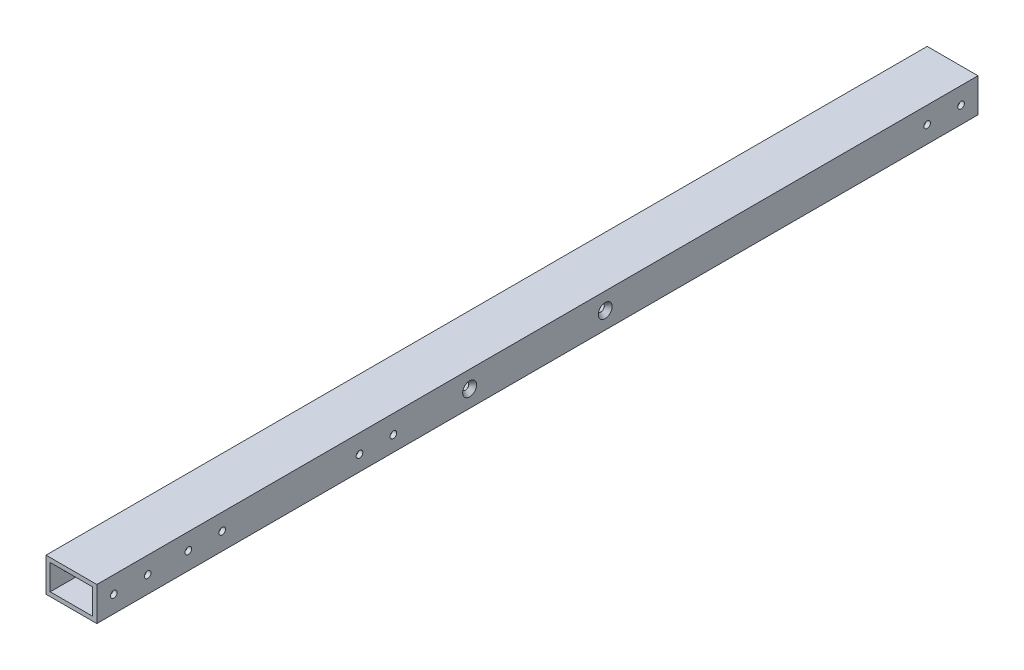
SolidWorks part; units mm, degrees
ref_plane "Front Plane" through (0, 0, 0) normal (0, 0, 1) x (1, 0, 0)
ref_plane "Top Plane" through (0, 0, 0) normal (0, 1, 0) x (1, 0, 0)
ref_plane "Right Plane" through (0, 0, 0) normal (1, 0, 0) x (0, 0, -1)
sketch "Sketch1" plane through (0, 0, 0) normal (0, 0, 1) x (1, 0, 0)
  line L0 (-15.875, 9.525) -> (15.875, 9.525)
  line L2 (-19.05, 12.7) -> (19.05, 12.7)
  line L3 (-19.05, 12.7) -> (-19.05, -12.7)
  line L4 (-19.05, -12.7) -> (19.05, -12.7)
  line L5 (19.05, 12.7) -> (19.05, -12.7)
  line L10 (15.875, 9.525) -> (15.875, -9.525)
  line L11 (-15.875, -9.525) -> (15.875, -9.525)
  line L12 (-15.875, 9.525) -> (-15.875, -9.525)
  point P12 (0, 12.7)
  point P14 (19.05, 0)
  dimension "Wall Thickness" = 3.175
  dimension "Outside Width" = 38.1
  dimension "Outside Height" = 25.4
  dimension "Inside Height" = 19.05
  dimension "Inside Width" = 31.75
sketch "Sketch2" plane through (0, 0, 0) normal (1, 0, 0) x (0, 0, -1)
  line L0 (330.2, 0) -> (-330.2, 0)
  point P4 (0, 0)
  point P7 (-330.2, 0)
  point P10 (330.2, 0)
  dimension "Length" = 660.4
sketch "Sketch3" plane through (0, 0, 0) normal (0, 0, 1) x (1, 0, 0)
  line L21 (19.05, 12.7) -> (-19.05, 12.7)
  line L22 (19.05, -12.7) -> (19.05, 12.7)
  line L23 (-19.05, -12.7) -> (19.05, -12.7)
  line L24 (-19.05, 12.7) -> (-19.05, -12.7)
  line L25 (19.05, 12.7) -> (-19.05, 12.7)
  line L26 (19.05, -12.7) -> (19.05, 12.7)
  line L27 (-19.05, -12.7) -> (19.05, -12.7)
  line L28 (-19.05, 12.7) -> (-19.05, -12.7)
  line L29 (15.875, 9.525) -> (-15.875, 9.525)
  line L30 (15.875, -9.525) -> (15.875, 9.525)
  line L31 (-15.875, -9.525) -> (15.875, -9.525)
  line L32 (-15.875, 9.525) -> (-15.875, -9.525)
  line L33 (15.875, 9.525) -> (-15.875, 9.525)
  line L34 (15.875, -9.525) -> (15.875, 9.525)
  line L35 (-15.875, -9.525) -> (15.875, -9.525)
  line L36 (-15.875, 9.525) -> (-15.875, -9.525)
  dimension "D1" = 0
  dimension "D2" = 0
extrude "Boss-Extrude1" add sketch "Sketch3" along normal up to vertex (330.2 mm away) and the other way up to vertex (330.2 mm away) up to point (0, 0, 330.2) other way up to point (0, 0, -330.2)
sketch "Drawing Reference" plane through (0, 0, 0) normal (1, 0, 0) x (0, 0, -1)
  line L0 (-330.2, 0) -> (330.2, 0) construction
  line L1 (0, -12.7) -> (0, 12.7) construction
  line L2 (-330.2, -12.7) -> (330.2, -12.7) construction
  line L5 (-330.2, 12.7) -> (330.2, 12.7) construction
  point P7 (-302.768, 0)
  point P8 (302.768, 0)
  dimension "D1" = 27.432
sketch "Sketch4" plane through (-19.05, 0, 0) normal (-1, 0, 0) x (0, 0, 1)
  line L0 (-330.2, 0) -> (-317.5, 0)
  line L1 (-330.2, 12.7) -> (-330.2, -12.7) construction
  line L2 (-317.5, 0) -> (-292.1, 0)
  line L3 (330.2, 12.7) -> (330.2, -12.7) construction
  line L4 (330.2, 0) -> (317.5, 0)
  line L5 (317.5, 0) -> (292.1, 0)
  line L6 (0, 0) -> (50.8, 0) construction
  line L7 (0, 0) -> (-50.8, 0) construction
  point P11 (-317.5, 0)
  point P13 (-292.1, 0)
  point P14 (317.5, 0)
  point P15 (292.1, 0)
  point P17 (0, 0)
  point P19 (0, 0)
  point P20 (0, 0)
  point P21 (0, 0)
hole_wizard "#10 Clearance Hole2" positions "Sketch11" profile "Sketch12" hole size "#10" standard "ANSI Inch" end condition through all
sketch "Sketch11" plane through (-19.05, 0, 0) normal (-1, 0, 0) x (0, 0, 1)
  point P0 (-317.5, 0)
  point P3 (-292.1, 0)
  point P6 (292.1, 0)
  point P9 (317.5, 0)
sketch "Sketch12" plane through (-19.05, 0, -317.5) normal (0, 1, 0) x (0, 0, 1)
  line L0 (0, 0) -> (0, 38.1)
  line L1 (0, 38.1) -> (2.4892, 38.1)
  line L2 (2.4892, 38.1) -> (2.4892, 0)
  line L5 (2.4892, 0) -> (0, 0)
  line L11 (0, -6.35) -> (0, 107.95) construction
  dimension "Thru Hole Dia." = 4.9784
  dimension "Thru Hole Depth" = 38.1
hole_wizard "#10 Clearance Hole5" positions "Sketch14" profile "Sketch16" hole size "#10" standard "ANSI Inch" end condition through all
sketch "Sketch14" plane through (19.05, 0, 0) normal (1, 0, 0) x (0, 0, -1)
  point P10 (-133.3405, -1.2316)
  point P13 (-107.9405, -1.2316)
  point P17 (-261.6105, 0.3559)
  point P20 (-236.2105, 0.3559)
sketch "Sketch16" plane through (19.05, -1.2316, 133.3405) normal (0, 1, 0) x (0, 0, -1)
  line L0 (0, 0) -> (0, 38.1)
  line L1 (0, 38.1) -> (2.4892, 38.1)
  line L2 (2.4892, 38.1) -> (2.4892, 0)
  line L5 (2.4892, 0) -> (0, 0)
  line L11 (0, -6.35) -> (0, 107.95) construction
  dimension "Thru Hole Dia." = 4.9784
  dimension "Thru Hole Depth" = 38.1
sketch "Sketch17" plane through (19.05, 0, 0) normal (1, 0, 0) x (0, 0, -1)
  point P0 (-261.6105, 0.3559)
  point P1 (-236.2105, 0.3559)
hole_wizard "#10 Clearance Hole4" positions "Sketch18" profile "Sketch19" hole size "#10" standard "ANSI Inch" end condition through all
sketch "Sketch18" plane through (19.05, 0, 0) normal (1, 0, 0) x (0, 0, -1)
  point P0 (-261.6105, 0.3559)
  point P3 (-236.2105, 0.3559)
sketch "Sketch19" plane through (19.05, 0.3559, 261.6105) normal (0, 1, 0) x (0, 0, -1)
  line L0 (0, 0) -> (0, 38.1)
  line L1 (0, 38.1) -> (2.4892, 38.1)
  line L2 (2.4892, 38.1) -> (2.4892, 0)
  line L5 (2.4892, 0) -> (0, 0)
  line L11 (0, -6.35) -> (0, 107.95) construction
  dimension "Thru Hole Dia." = 4.9784
  dimension "Thru Hole Depth" = 38.1
hole_wizard "#10 Clearance Hole3" positions "Sketch20" profile "Sketch21" hole size "#10" standard "ANSI Inch" end condition through all
sketch "Sketch20" plane through (-19.05, 0, 0) normal (-1, 0, 0) x (0, 0, 1)
  point P0 (-50.8, 0)
  point P3 (50.8, 0)
sketch "Sketch21" plane through (-19.05, 0, -50.8) normal (0, 1, 0) x (0, 0, 1)
  line L0 (0, 0) -> (0, 38.1)
  line L1 (0, 38.1) -> (5.207, 38.1)
  line L2 (2.4892, 34.9735) -> (2.4892, 0)
  line L5 (2.4892, 0) -> (0, 0)
  line L7 (5.207, 38.1) -> (2.4892, 34.9735)
  line L8 (-5.207, 38.1) -> (-2.4892, 34.9735) construction
  line L11 (0, -6.35) -> (0, 107.95) construction
  dimension "Thru Hole Dia." = 4.9784
  dimension "Thru Hole Depth" = 38.1
  dimension "Far C'Sink Dia." = 10.414
  dimension "Far C'Sink Angle" = 82
equation "\"D1@Drawing Reference\"=\"Outside Width@Sketch1\" * 0.72"
